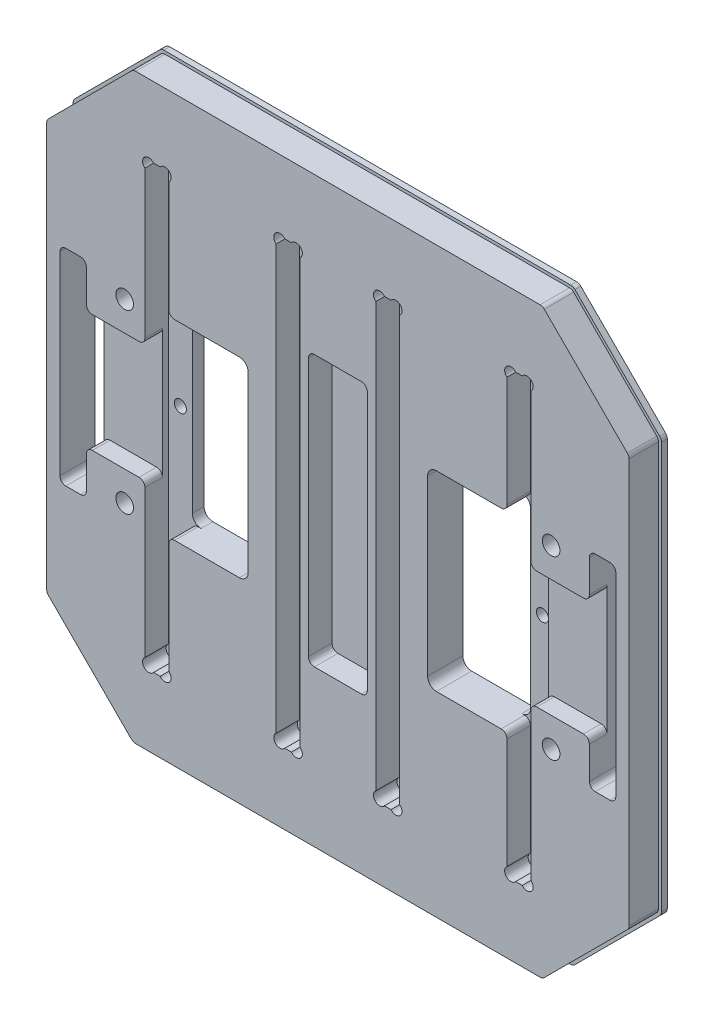
SolidWorks part; units mm, degrees
ref_plane "Front" through (0, 0, 0) normal (0, 0, 1) x (1, 0, 0)
ref_plane "Top" through (0, 0, 0) normal (0, 1, 0) x (1, 0, 0)
ref_plane "Right" through (0, 0, 0) normal (1, 0, 0) x (0, 0, -1)
sketch "Esquisse2" plane through (0, 0, 0) normal (0, 0, 1) x (1, 0, 0)
  line L1 (0, 0) -> (200, 0)
  line L2 (0, 0) -> (0, 200)
  line L3 (0, 200) -> (200, 200)
  line L4 (200, 0) -> (200, 200)
  dimension "D1" = 200
  dimension "D2" = 200
extrude "Boss.-Extru.1" add sketch "Esquisse2" along normal blind 12
sketch "Esquisse3" plane through (0, 0, 12) normal (0, 0, 1) x (1, 0, 0)
  line L0 (0, 100) -> (200, 100) construction
  line L1 (0, 200) -> (0, 0) construction
  line L2 (200, 0) -> (200, 200) construction
  line L3 (0, 0) -> (200, 0) construction
  line L4 (100, 100) -> (100, 198.2097) construction
  line L5 (185.5, 67) -> (185.5, 133)
  line L6 (187.5, 135) -> (192.5, 135)
  line L7 (194.5, 133) -> (194.5, 67)
  line L8 (187.5, 65) -> (192.5, 65)
  line L9 (12.5, 65) -> (7.5, 65)
  line L10 (5.5, 133) -> (5.5, 67)
  line L11 (12.5, 135) -> (7.5, 135)
  line L12 (14.5, 67) -> (14.5, 133)
  line L13 (69.5, 70.5) -> (69.5, 129.5)
  line L14 (66.5, 132.5) -> (45.5, 132.5)
  line L15 (42.5, 129.5) -> (42.5, 70.5)
  line L16 (190, 135) -> (190, 163.9784) construction
  line L17 (190, 163.9784) -> (100, 163.9784) construction
  line L18 (56, 132.5) -> (56, 150.9164) construction
  line L19 (56, 150.9164) -> (100, 150.9164) construction
  line L20 (66.5, 67.5) -> (45.5, 67.5)
  line L21 (133.5, 67.5) -> (154.5, 67.5)
  line L22 (157.5, 129.5) -> (157.5, 70.5)
  line L23 (133.5, 132.5) -> (154.5, 132.5)
  line L24 (130.5, 70.5) -> (130.5, 129.5)
  circle A0 centre (172.5, 130) radius 3
  circle A1 centre (172.5, 70) radius 3
  circle A2 centre (27.5, 70) radius 3
  circle A3 centre (27.5, 130) radius 3
  arc A4 (192.5, 65) -> (194.5, 67) centre (192.5, 67) ccw
  arc A5 (187.5, 65) -> (185.5, 67) centre (187.5, 67) cw
  arc A6 (192.5, 135) -> (194.5, 133) centre (192.5, 133) cw
  arc A7 (185.5, 133) -> (187.5, 135) centre (187.5, 133) cw
  arc A8 (12.5, 65) -> (14.5, 67) centre (12.5, 67) ccw
  arc A9 (7.5, 65) -> (5.5, 67) centre (7.5, 67) cw
  arc A10 (12.5, 135) -> (14.5, 133) centre (12.5, 133) cw
  arc A11 (5.5, 133) -> (7.5, 135) centre (7.5, 133) cw
  arc A12 (133.5, 67.5) -> (130.5, 70.5) centre (133.5, 70.5) cw
  arc A13 (154.5, 67.5) -> (157.5, 70.5) centre (154.5, 70.5) ccw
  arc A14 (157.5, 129.5) -> (154.5, 132.5) centre (154.5, 129.5) ccw
  arc A15 (133.5, 132.5) -> (130.5, 129.5) centre (133.5, 129.5) ccw
  arc A16 (66.5, 67.5) -> (69.5, 70.5) centre (66.5, 70.5) ccw
  arc A17 (45.5, 67.5) -> (42.5, 70.5) centre (45.5, 70.5) cw
  arc A18 (69.5, 129.5) -> (66.5, 132.5) centre (66.5, 129.5) ccw
  arc A19 (45.5, 132.5) -> (42.5, 129.5) centre (45.5, 129.5) ccw
  point P23 (194.5, 100)
  point P24 (185.5, 100)
  point P28 (14.5, 100)
  point P29 (5.5, 100)
  point P41 (42.5, 100)
  point P42 (69.5, 100)
  point P46 (130.5, 100)
  point P47 (157.5, 100)
  point P50 (194.5, 65)
  point P53 (185.5, 65)
  point P56 (194.5, 135)
  point P59 (185.5, 135)
  point P62 (14.5, 65)
  point P65 (5.5, 65)
  point P68 (14.5, 135)
  point P71 (5.5, 135)
  point P74 (130.5, 67.5)
  point P77 (157.5, 67.5)
  point P80 (157.5, 132.5)
  point P83 (130.5, 132.5)
  point P86 (69.5, 67.5)
  point P89 (42.5, 67.5)
  point P92 (69.5, 132.5)
  point P95 (42.5, 132.5)
  dimension "D2" = 60
  dimension "D3" = 44
  dimension "D4" = 6
  dimension "D11" = 2
  dimension "D12" = 3
  dimension "D1" = 100
  dimension "D5" = 9
  dimension "D6" = 13
  dimension "D7" = 70
  dimension "D8" = 90
  dimension "D9" = 65
  dimension "D10" = 27
extrude "Enlèv. mat.-Extru.1" cut sketch "Esquisse3" against normal through all both and the other way through all
chamfer "Chanfrein1" distance 30 distance2 30 4 edges at (0, 200, 6) (200, 200, 6) (200, 0, 6) (0, 0, 6)
sketch "Esquisse4" plane through (0, 0, 12) normal (0, 0, 1) x (1, 0, 0)
  line L16 (169.5858, 199) -> (30.4142, 199)
  line L17 (30.4142, 199) -> (1, 169.5858)
  line L18 (1, 169.5858) -> (1, 30.4142)
  line L19 (1, 30.4142) -> (30.4142, 1)
  line L20 (30.4142, 1) -> (169.5858, 1)
  line L21 (169.5858, 1) -> (199, 30.4142)
  line L22 (199, 30.4142) -> (199, 169.5858)
  line L23 (199, 169.5858) -> (169.5858, 199)
  line L24 (169.5858, 199) -> (30.4142, 199)
  line L25 (30.4142, 199) -> (1, 169.5858)
  line L26 (1, 169.5858) -> (1, 30.4142)
  line L27 (1, 30.4142) -> (30.4142, 1)
  line L28 (30.4142, 1) -> (169.5858, 1)
  line L29 (169.5858, 1) -> (199, 30.4142)
  line L30 (199, 30.4142) -> (199, 169.5858)
  line L31 (199, 169.5858) -> (169.5858, 199)
  line L32 (170, 200) -> (30, 200)
  line L33 (30, 200) -> (0, 170)
  line L34 (0, 170) -> (0, 30)
  line L35 (0, 30) -> (30, 0)
  line L36 (30, 0) -> (170, 0)
  line L37 (170, 0) -> (200, 30)
  line L38 (200, 30) -> (200, 170)
  line L39 (200, 170) -> (170, 200)
  line L40 (170, 200) -> (30, 200)
  line L41 (30, 200) -> (0, 170)
  line L42 (0, 170) -> (0, 30)
  line L43 (0, 30) -> (30, 0)
  line L44 (30, 0) -> (170, 0)
  line L45 (170, 0) -> (200, 30)
  line L46 (200, 30) -> (200, 170)
  line L47 (200, 170) -> (170, 200)
  dimension "D1" = 1
  dimension "D2" = 0
extrude "Enlèv. mat.-Extru.2" cut sketch "Esquisse4" against normal blind 10
sketch "Esquisse5" plane through (0, 0, 12) normal (0, 0, 1) x (1, 0, 0)
  line L0 (100, 0) -> (100, 100) construction
  line L1 (14.5, 120) -> (14.5, 80)
  line L2 (165.5, 120) -> (185.5, 120)
  line L3 (165.5, 120) -> (165.5, 80)
  line L4 (165.5, 80) -> (185.5, 80)
  line L5 (30, 0) -> (170, 0) construction
  line L6 (100, 100) -> (165.5, 100) construction
  line L7 (185.5, 120) -> (185.5, 80)
  line L8 (100, 100) -> (69.5, 100) construction
  line L9 (69.5, 70.5) -> (69.5, 129.5) construction
  line L10 (34.5, 80) -> (14.5, 80)
  line L11 (34.5, 120) -> (34.5, 80)
  line L12 (34.5, 120) -> (14.5, 120)
  dimension "D1" = 40
  dimension "D2" = 65.5
  dimension "D3" = 20
extrude "Enlèv. mat.-Extru.3" cut sketch "Esquisse5" against normal blind 6
sketch "Esquisse6" plane through (0, 0, 12) normal (0, 0, 1) x (1, 0, 0)
  line L0 (69.5, 100) -> (130.5, 100) construction
  line L1 (157.5, 175) -> (165.62, 175)
  line L2 (157.5, 175) -> (157.5, 25)
  line L3 (157.5, 25) -> (165.62, 25)
  line L4 (165.62, 175) -> (165.62, 25)
  line L5 (69.5, 70.5) -> (69.5, 129.5) construction
  line L6 (130.5, 129.5) -> (130.5, 70.5) construction
  line L7 (100, 100) -> (100, 191.362) construction
  line L8 (130.5, 100) -> (157.5, 100) construction
  line L9 (157.5, 70.5) -> (157.5, 129.5) construction
  line L10 (34.38, 175) -> (34.38, 25)
  line L11 (42.5, 25) -> (34.38, 25)
  line L12 (42.5, 175) -> (42.5, 25)
  line L13 (42.5, 175) -> (34.38, 175)
  line L14 (112.88, 100) -> (100, 100) construction
  line L15 (112.88, 175) -> (121, 175)
  line L16 (112.88, 175) -> (112.88, 25)
  line L17 (112.88, 25) -> (121, 25)
  line L18 (121, 175) -> (121, 25)
  line L19 (79, 175) -> (79, 25)
  line L20 (87.12, 25) -> (79, 25)
  line L21 (87.12, 175) -> (87.12, 25)
  line L22 (87.12, 175) -> (79, 175)
  dimension "D1" = 150
  dimension "D2" = 8.12
  dimension "D3" = 8.12
  dimension "D4" = 150
  dimension "D5" = 21
extrude "Enlèv. mat.-Extru.4" cut sketch "Esquisse6" against normal blind 8
sketch "Esquisse7" plane through (0, 0, 12) normal (0, 0, 1) x (1, 0, 0)
  line L0 (87.12, 100) -> (112.88, 100) construction
  line L1 (87.12, 25) -> (87.12, 175) construction
  line L2 (112.88, 175) -> (112.88, 25) construction
  line L3 (100, 100) -> (100, 199) construction
  line L4 (169.5858, 199) -> (30.4142, 199) construction
  line L5 (114.18, 173.7) -> (112.88, 175) construction
  line L6 (121, 175) -> (112.88, 175) construction
  line L7 (116.94, 175) -> (116.94, 100) construction
  line L8 (121, 175) -> (112.88, 175) construction
  line L9 (116.94, 100) -> (112.88, 100) construction
  line L10 (119.7, 173.7) -> (121, 175) construction
  line L11 (119.7, 26.3) -> (121, 25) construction
  line L12 (114.18, 26.3) -> (112.88, 25) construction
  line L13 (116.94, 100) -> (139.25, 100) construction
  line L14 (139.25, 100) -> (139.25, 192.3771) construction
  line L15 (164.32, 26.3) -> (165.62, 25) construction
  line L16 (158.8, 26.3) -> (157.5, 25) construction
  line L17 (158.8, 173.7) -> (157.5, 175) construction
  line L18 (161.56, 100) -> (165.62, 100) construction
  line L19 (161.56, 175) -> (161.56, 100) construction
  line L20 (164.32, 173.7) -> (165.62, 175) construction
  line L21 (165.62, 175) -> (157.5, 175) construction
  line L22 (35.68, 173.7) -> (34.38, 175) construction
  line L23 (38.44, 175) -> (38.44, 100) construction
  line L24 (38.44, 100) -> (34.38, 100) construction
  line L25 (41.2, 173.7) -> (42.5, 175) construction
  line L26 (41.2, 26.3) -> (42.5, 25) construction
  line L27 (35.68, 26.3) -> (34.38, 25) construction
  line L28 (60.75, 100) -> (60.75, 192.3771) construction
  line L29 (83.06, 100) -> (60.75, 100) construction
  line L30 (85.82, 26.3) -> (87.12, 25) construction
  line L31 (80.3, 26.3) -> (79, 25) construction
  line L32 (80.3, 173.7) -> (79, 175) construction
  line L33 (83.06, 100) -> (87.12, 100) construction
  line L34 (83.06, 175) -> (83.06, 100) construction
  line L35 (85.82, 173.7) -> (87.12, 175) construction
  circle A0 centre (114.18, 173.7) radius 2.1
  circle A1 centre (119.7, 173.7) radius 2.1
  circle A2 centre (119.7, 26.3) radius 2.1
  circle A3 centre (114.18, 26.3) radius 2.1
  circle A4 centre (164.32, 26.3) radius 2.1
  circle A5 centre (158.8, 26.3) radius 2.1
  circle A6 centre (158.8, 173.7) radius 2.1
  circle A7 centre (164.32, 173.7) radius 2.1
  circle A8 centre (35.68, 173.7) radius 2.1
  circle A9 centre (41.2, 173.7) radius 2.1
  circle A10 centre (41.2, 26.3) radius 2.1
  circle A11 centre (35.68, 26.3) radius 2.1
  circle A12 centre (85.82, 26.3) radius 2.1
  circle A13 centre (80.3, 26.3) radius 2.1
  circle A14 centre (80.3, 173.7) radius 2.1
  circle A15 centre (85.82, 173.7) radius 2.1
  dimension "D1" = 4.2
  dimension "D2" = 1.3
  dimension "D3" = 1.3
extrude "Enlèv. mat.-Extru.5" cut sketch "Esquisse7" against normal up to vertex (8 mm away) up to point (112.88, 25, 4)
sketch "Esquisse8" plane through (0, 0, 12) normal (0, 0, 1) x (1, 0, 0)
  line L0 (100, 1) -> (100, 199) construction
  line L1 (30.4142, 1) -> (169.5858, 1) construction
  line L2 (169.5858, 199) -> (30.4142, 199) construction
  line L3 (100, 100) -> (252.8445, 100) construction
  line L4 (110, 54) -> (110, 146)
  line L5 (110, 146) -> (90, 146)
  line L6 (90, 54) -> (90, 146)
  line L7 (110, 54) -> (90, 54)
  point P8 (100, 54)
  point P12 (100, 146)
  point P14 (90, 100)
  point P15 (110, 100)
  dimension "D1" = 20
  dimension "D2" = 92
extrude "Enlèv. mat.-Extru.6" cut sketch "Esquisse8" against normal blind 8
sketch "Esquisse10" plane through (0, 0, 12) normal (0, 0, 1) x (1, 0, 0)
  line L0 (45.5, 132.5) -> (42.5, 132.5)
  line L1 (42.5, 129.5) -> (42.5, 172.0508) construction
  line L2 (42.5, 132.5) -> (42.5, 129.5)
  line L3 (42.5, 129.5) -> (45.5, 132.5)
  line L4 (42.5, 100) -> (69.5, 100) construction
  line L5 (42.5, 70.5) -> (42.5, 129.5) construction
  line L6 (69.5, 70.5) -> (69.5, 129.5) construction
  line L7 (100, 54) -> (100, 146) construction
  line L8 (90, 54) -> (110, 54) construction
  line L9 (110, 146) -> (90, 146) construction
  line L10 (42.5, 70.5) -> (45.5, 67.5)
  line L11 (42.5, 67.5) -> (42.5, 70.5)
  line L12 (45.5, 67.5) -> (42.5, 67.5)
  line L13 (154.5, 67.5) -> (157.5, 67.5)
  line L14 (157.5, 67.5) -> (157.5, 70.5)
  line L15 (157.5, 70.5) -> (154.5, 67.5)
  line L16 (157.5, 129.5) -> (154.5, 132.5)
  line L17 (157.5, 132.5) -> (157.5, 129.5)
  line L18 (154.5, 132.5) -> (157.5, 132.5)
extrude "Enlèv. mat.-Extru.8" cut sketch "Esquisse10" against normal up to vertex (8 mm away) up to point (157.5, 129.5, 4)
sketch "Esquisse11" [suppressed] plane through (0, 0, 6) normal (0, 0, 1) x (1, 0, 0)
  line L0 (28.4, 100) -> (34.4, 100) construction
  line L1 (17.4, 115) -> (28.4, 115)
  line L2 (17.4, 115) -> (17.4, 85)
  line L3 (17.4, 85) -> (28.4, 85)
  line L4 (28.4, 115) -> (28.4, 85)
  line L5 (34.4, 120) -> (34.4, 80) construction
  line L6 (100, 1) -> (100, 159.2856) construction
  line L7 (30.4142, 1) -> (169.5858, 1) construction
  line L8 (171.6, 115) -> (171.6, 85)
  line L9 (182.6, 85) -> (171.6, 85)
  line L10 (182.6, 115) -> (182.6, 85)
  line L11 (182.6, 115) -> (171.6, 115)
  dimension "D1" = 6
  dimension "D2" = 11
  dimension "D3" = 30
extrude "Enlèv. mat.-Extru.9" [suppressed] cut sketch "Esquisse11" against normal through all both and the other way through all
fillet "Congé1" radius 2 16 edges at (110, 54, 8) (90, 54, 8) (110, 146, 8) (90, 146, 8) (165.62, 120, 9) (185.5, 120, 9) (185.5, 80, 9) (165.62, 80, 9) (34.38, 80, 9) (14.5, 80, 9) (34.38, 120, 9) (14.5, 120, 9) (42.5, 67.5, 8) (42.5, 132.5, 8) (157.5, 132.5, 8) (157.5, 67.5, 8)
fillet "Congé2" radius 2 16 edges at (1, 169.5858, 7) (30.4142, 199, 7) (169.5858, 199, 7) (199, 169.5858, 7) (199, 30.4142, 7) (169.5858, 1, 7) (1, 30.4142, 7) (30.4142, 1, 7) (170, 200, 1) (200, 170, 1) (200, 30, 1) (170, 0, 1) (30, 0, 1) (0, 30, 1) (0, 170, 1) (30, 200, 1)
sketch "Esquisse9" [suppressed] plane through (0, 0, 12) normal (0, 0, 1) x (1, 0, 0)
  line L0 (22.7574, 205.4853) -> (-5.4853, 177.2426)
  line L1 (-9, 168.7574) -> (-9, 31.2426)
  line L2 (-5.4853, 22.7574) -> (22.7574, -5.4853)
  line L3 (31.2426, -9) -> (168.7574, -9)
  line L4 (177.2426, -5.4853) -> (205.4853, 22.7574)
  line L5 (209, 31.2426) -> (209, 168.7574)
  line L6 (205.4853, 177.2426) -> (177.2426, 205.4853)
  line L7 (168.7574, 209) -> (31.2426, 209)
  line L8 (29.8284, 198.4142) -> (1.5858, 170.1716)
  line L9 (1, 168.7574) -> (1, 31.2426)
  line L10 (1.5858, 29.8284) -> (29.8284, 1.5858)
  line L11 (31.2426, 1) -> (168.7574, 1)
  line L12 (170.1716, 1.5858) -> (198.4142, 29.8284)
  line L13 (199, 31.2426) -> (199, 168.7574)
  line L14 (198.4142, 170.1716) -> (170.1716, 198.4142)
  line L15 (168.7574, 199) -> (31.2426, 199)
  line L16 (29.8284, 198.4142) -> (1.5858, 170.1716)
  line L17 (1, 168.7574) -> (1, 31.2426)
  line L18 (1.5858, 29.8284) -> (29.8284, 1.5858)
  line L19 (31.2426, 1) -> (168.7574, 1)
  line L20 (170.1716, 1.5858) -> (198.4142, 29.8284)
  line L21 (199, 31.2426) -> (199, 168.7574)
  line L22 (198.4142, 170.1716) -> (170.1716, 198.4142)
  line L23 (168.7574, 199) -> (31.2426, 199)
  arc A0 (-5.4853, 177.2426) -> (-9, 168.7574) centre (3, 168.7574) ccw
  arc A1 (-9, 31.2426) -> (-5.4853, 22.7574) centre (3, 31.2426) ccw
  arc A2 (22.7574, -5.4853) -> (31.2426, -9) centre (31.2426, 3) ccw
  arc A3 (168.7574, -9) -> (177.2426, -5.4853) centre (168.7574, 3) ccw
  arc A4 (205.4853, 22.7574) -> (209, 31.2426) centre (197, 31.2426) ccw
  arc A5 (209, 168.7574) -> (205.4853, 177.2426) centre (197, 168.7574) ccw
  arc A6 (177.2426, 205.4853) -> (168.7574, 209) centre (168.7574, 197) ccw
  arc A7 (31.2426, 209) -> (22.7574, 205.4853) centre (31.2426, 197) ccw
  arc A8 (1.5858, 170.1716) -> (1, 168.7574) centre (3, 168.7574) ccw
  arc A9 (1, 31.2426) -> (1.5858, 29.8284) centre (3, 31.2426) ccw
  arc A10 (29.8284, 1.5858) -> (31.2426, 1) centre (31.2426, 3) ccw
  arc A11 (168.7574, 1) -> (170.1716, 1.5858) centre (168.7574, 3) ccw
  arc A12 (198.4142, 29.8284) -> (199, 31.2426) centre (197, 31.2426) ccw
  arc A13 (199, 168.7574) -> (198.4142, 170.1716) centre (197, 168.7574) ccw
  arc A14 (170.1716, 198.4142) -> (168.7574, 199) centre (168.7574, 197) ccw
  arc A15 (31.2426, 199) -> (29.8284, 198.4142) centre (31.2426, 197) ccw
  arc A16 (1.5858, 170.1716) -> (1, 168.7574) centre (3, 168.7574) ccw
  arc A17 (1, 31.2426) -> (1.5858, 29.8284) centre (3, 31.2426) ccw
  arc A18 (29.8284, 1.5858) -> (31.2426, 1) centre (31.2426, 3) ccw
  arc A19 (168.7574, 1) -> (170.1716, 1.5858) centre (168.7574, 3) ccw
  arc A20 (198.4142, 29.8284) -> (199, 31.2426) centre (197, 31.2426) ccw
  arc A21 (199, 168.7574) -> (198.4142, 170.1716) centre (197, 168.7574) ccw
  arc A22 (170.1716, 198.4142) -> (168.7574, 199) centre (168.7574, 197) ccw
  arc A23 (31.2426, 199) -> (29.8284, 198.4142) centre (31.2426, 197) ccw
  dimension "D1" = 0
  dimension "D2" = 10
extrude "Enlèv. mat.-Extru.7" [suppressed] cut sketch "Esquisse9" against normal through all both and the other way through all
fillet "Congé3" [suppressed] radius 2
sketch "Esquisse12" [suppressed] plane through (0, 0, 0) normal (0, 0, -1) x (-1, 0, 0)
  line L0 (-69.5, 70.5) -> (-69.5, 129.5) construction
  line L1 (-66.5, 132.5) -> (-45.5, 132.5) construction
  line L2 (-42.5, 129.5) -> (-42.5, 70.5) construction
  line L3 (-45.5, 67.5) -> (-66.5, 67.5) construction
  line L4 (-133.5, 67.5) -> (-154.5, 67.5) construction
  line L5 (-130.5, 129.5) -> (-130.5, 70.5) construction
  line L6 (-154.5, 132.5) -> (-133.5, 132.5) construction
  line L7 (-157.5, 70.5) -> (-157.5, 129.5) construction
  line L8 (-69.5, 70.5) -> (-69.5, 129.5)
  line L9 (-66.5, 132.5) -> (-45.5, 132.5)
  line L10 (-42.5, 129.5) -> (-42.5, 70.5)
  line L11 (-45.5, 67.5) -> (-66.5, 67.5)
  line L12 (-133.5, 67.5) -> (-154.5, 67.5)
  line L13 (-130.5, 129.5) -> (-130.5, 70.5)
  line L14 (-154.5, 132.5) -> (-133.5, 132.5)
  line L15 (-157.5, 70.5) -> (-157.5, 129.5)
  arc A0 (-66.5, 132.5) -> (-69.5, 129.5) centre (-66.5, 129.5) ccw construction
  arc A1 (-42.5, 129.5) -> (-45.5, 132.5) centre (-45.5, 129.5) ccw construction
  arc A2 (-45.5, 67.5) -> (-42.5, 70.5) centre (-45.5, 70.5) ccw construction
  arc A3 (-69.5, 70.5) -> (-66.5, 67.5) centre (-66.5, 70.5) ccw construction
  arc A4 (-157.5, 70.5) -> (-154.5, 67.5) centre (-154.5, 70.5) ccw construction
  arc A5 (-133.5, 67.5) -> (-130.5, 70.5) centre (-133.5, 70.5) ccw construction
  arc A6 (-130.5, 129.5) -> (-133.5, 132.5) centre (-133.5, 129.5) ccw construction
  arc A7 (-154.5, 132.5) -> (-157.5, 129.5) centre (-154.5, 129.5) ccw construction
  arc A8 (-66.5, 132.5) -> (-69.5, 129.5) centre (-66.5, 129.5) ccw
  arc A9 (-42.5, 129.5) -> (-45.5, 132.5) centre (-45.5, 129.5) ccw
  arc A10 (-45.5, 67.5) -> (-42.5, 70.5) centre (-45.5, 70.5) ccw
  arc A11 (-69.5, 70.5) -> (-66.5, 67.5) centre (-66.5, 70.5) ccw
  arc A12 (-157.5, 70.5) -> (-154.5, 67.5) centre (-154.5, 70.5) ccw
  arc A13 (-133.5, 67.5) -> (-130.5, 70.5) centre (-133.5, 70.5) ccw
  arc A14 (-130.5, 129.5) -> (-133.5, 132.5) centre (-133.5, 129.5) ccw
  arc A15 (-154.5, 132.5) -> (-157.5, 129.5) centre (-154.5, 129.5) ccw
extrude "Boss.-Extru.2" [suppressed] add sketch "Esquisse12" against normal up to vertex up to point (157.5, 129.5, 4)
sketch "Esquisse13" [suppressed] plane through (0, 0, 0) normal (0, 0, -1) x (-1, 0, 0)
  line L0 (-14.5, 67) -> (-14.5, 133) construction
  line L1 (-12.5, 135) -> (-7.5, 135) construction
  line L2 (-5.5, 133) -> (-5.5, 67) construction
  line L3 (-7.5, 65) -> (-12.5, 65) construction
  line L4 (-187.5, 65) -> (-192.5, 65) construction
  line L5 (-194.5, 67) -> (-194.5, 133) construction
  line L6 (-192.5, 135) -> (-187.5, 135) construction
  line L7 (-185.5, 133) -> (-185.5, 67) construction
  line L8 (-14.5, 67) -> (-14.5, 133)
  line L9 (-12.5, 135) -> (-7.5, 135)
  line L10 (-5.5, 133) -> (-5.5, 67)
  line L11 (-7.5, 65) -> (-12.5, 65)
  line L12 (-187.5, 65) -> (-192.5, 65)
  line L13 (-194.5, 67) -> (-194.5, 133)
  line L14 (-192.5, 135) -> (-187.5, 135)
  line L15 (-185.5, 133) -> (-185.5, 67)
  arc A0 (-14.5, 67) -> (-12.5, 65) centre (-12.5, 67) ccw construction
  arc A1 (-12.5, 135) -> (-14.5, 133) centre (-12.5, 133) ccw construction
  arc A2 (-5.5, 133) -> (-7.5, 135) centre (-7.5, 133) ccw construction
  arc A3 (-7.5, 65) -> (-5.5, 67) centre (-7.5, 67) ccw construction
  arc A4 (-187.5, 65) -> (-185.5, 67) centre (-187.5, 67) ccw construction
  arc A5 (-194.5, 67) -> (-192.5, 65) centre (-192.5, 67) ccw construction
  arc A6 (-192.5, 135) -> (-194.5, 133) centre (-192.5, 133) ccw construction
  arc A7 (-185.5, 133) -> (-187.5, 135) centre (-187.5, 133) ccw construction
  arc A8 (-14.5, 67) -> (-12.5, 65) centre (-12.5, 67) ccw
  arc A9 (-12.5, 135) -> (-14.5, 133) centre (-12.5, 133) ccw
  arc A10 (-5.5, 133) -> (-7.5, 135) centre (-7.5, 133) ccw
  arc A11 (-7.5, 65) -> (-5.5, 67) centre (-7.5, 67) ccw
  arc A12 (-187.5, 65) -> (-185.5, 67) centre (-187.5, 67) ccw
  arc A13 (-194.5, 67) -> (-192.5, 65) centre (-192.5, 67) ccw
  arc A14 (-192.5, 135) -> (-194.5, 133) centre (-192.5, 133) ccw
  arc A15 (-185.5, 133) -> (-187.5, 135) centre (-187.5, 133) ccw
extrude "Boss.-Extru.3" [suppressed] add sketch "Esquisse13" against normal up to vertex up to point (14.5, 78, 6)
sketch "Esquisse14" plane through (0, 0, 4) normal (0, 0, 1) x (1, 0, 0)
  line L0 (100, 54) -> (100, 146) construction
  line L1 (92, 54) -> (108, 54) construction
  line L2 (108, 146) -> (92, 146) construction
  line L3 (100, 100) -> (-15.2006, 100) construction
  line L4 (83.06, 160) -> (83.06, 175) construction
  line L5 (84.1708, 175) -> (81.9492, 175) construction
  line L7 (79, 150.5938) -> (42.5, 150.5938) construction
  line L8 (79, 172.0508) -> (79, 27.9492) construction
  line L9 (42.5, 134.5) -> (42.5, 172.0508) construction
  line L10 (60.75, 150.5938) -> (60.75, 164.7943) construction
  line L11 (83.06, 100) -> (83.06, 40) construction
  line L12 (38.44, 100) -> (38.44, 40) construction
  line L13 (38.44, 160) -> (38.44, 175) construction
  line L14 (161.56, 160) -> (161.56, 175) construction
  line L15 (161.56, 100) -> (161.56, 40) construction
  line L16 (116.94, 100) -> (116.94, 40) construction
  line L17 (139.25, 150.5938) -> (139.25, 164.7943) construction
  line L18 (121, 150.5938) -> (157.5, 150.5938) construction
  line L19 (116.94, 160) -> (116.94, 175) construction
  circle A0 centre (83.06, 160) radius 2.05
  circle A1 centre (83.06, 40) radius 2.05
  circle A2 centre (83.06, 100) radius 2.05
  circle A3 centre (38.44, 100) radius 2.05
  circle A4 centre (38.44, 40) radius 2.05
  circle A5 centre (38.44, 160) radius 2.05
  circle A6 centre (161.56, 160) radius 2.05
  circle A7 centre (161.56, 40) radius 2.05
  circle A8 centre (161.56, 100) radius 2.05
  circle A9 centre (116.94, 100) radius 2.05
  circle A10 centre (116.94, 40) radius 2.05
  circle A11 centre (116.94, 160) radius 2.05
  dimension "D1" = 60
  dimension "D2" = 4.1
extrude "Enlèv. mat.-Extru.10" cut sketch "Esquisse14" against normal through all both and the other way through all
